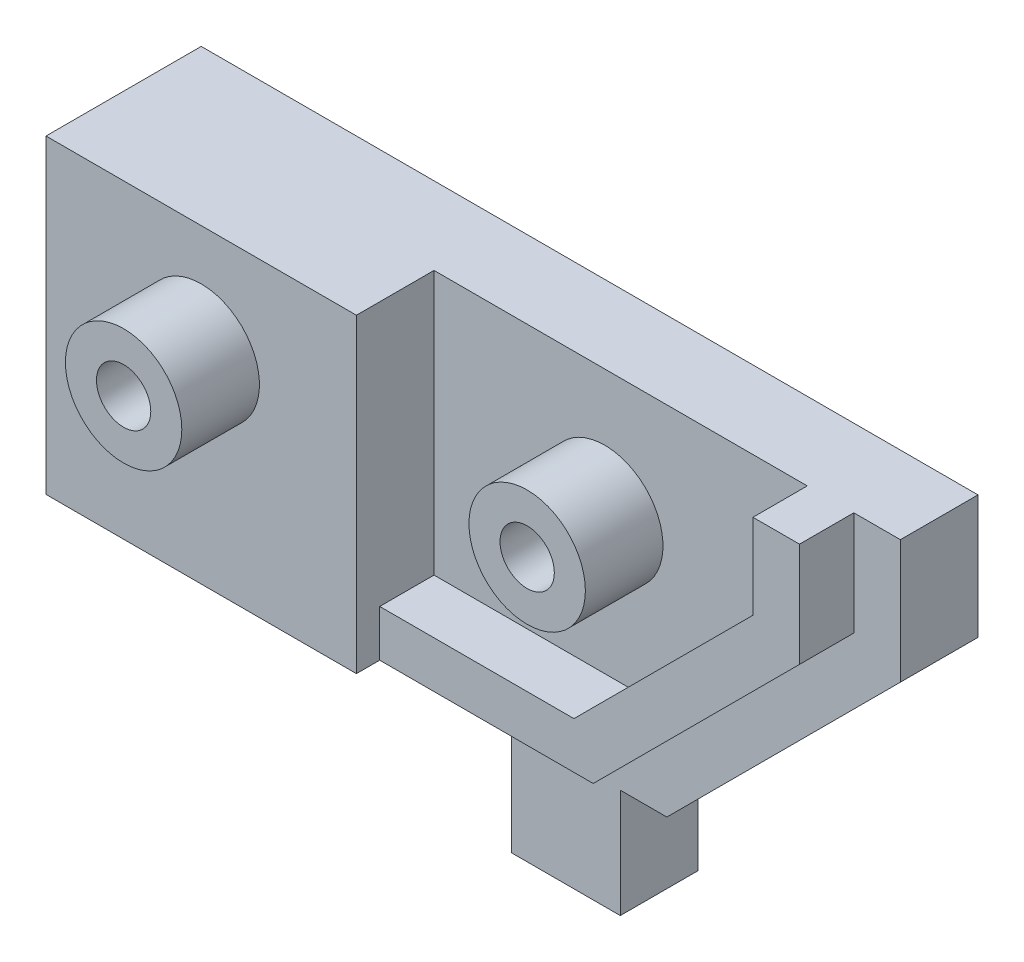
SolidWorks part; units mm, degrees
ref_plane "Front Plane" through (0, 0, 0) normal (0, 0, 1) x (1, 0, 0)
ref_plane "Top Plane" through (0, 0, 0) normal (0, 1, 0) x (1, 0, 0)
ref_plane "Right Plane" through (0, 0, 0) normal (1, 0, 0) x (0, 0, -1)
sketch "Sketch1" plane through (0, 0, 0) normal (0, 1, 0) x (1, 0, 0)
  line L10 (-18, -5.5617) -> (-18, -10) construction
  line L11 (0, 0) -> (-18, 0)
  line L12 (0, 0) -> (0, -5)
  line L13 (0, -5) -> (-15, -5)
  line L14 (-18, 0) -> (-18, -5.5617) construction
  line L16 (-15, -5) -> (-15, -10)
  line L17 (-15, -10) -> (-35, -10)
  line L18 (-35, -5) -> (-35, -10)
  line L19 (-18, 0) -> (-22, 0)
  line L21 (-35, -5) -> (-35, 0)
  line L22 (-35, 0) -> (-22, 0)
  dimension "D1" = 20
  dimension "D2" = 5
  dimension "D3" = 5
  dimension "D4" = 18
  dimension "D7" = 15
extrude "Boss-Extrude1" add sketch "Sketch1" along normal blind 23
sketch "Sketch2" plane through (0, 0, 10) normal (0, 0, 1) x (1, 0, 0)
  line L0 (-35, 23) -> (-35, 0) construction
  line L1 (-35, 0) -> (-15, 0) construction
  line L2 (-15, 0) -> (0, 0) construction
  line L3 (0, 23) -> (0, 0) construction
  circle A0 centre (-25, 16) radius 1.75
  circle A1 centre (-4, 15) radius 1.75
  dimension "D5" = 3.5
  dimension "D6" = 3.5
  dimension "D1" = 10
  dimension "D2" = 16
  dimension "D3" = 15
  dimension "D4" = 4
extrude "Cut-Extrude1" cut sketch "Sketch2" against normal through all
sketch "Sketch3" plane through (0, 0, 0) normal (0, -1, 0) x (1, 0, 0)
  line L0 (-25, 10) -> (-25, 0) construction
  line L1 (-35, 10) -> (-15, 10) construction
  line L3 (0, 0) -> (-35, 0) construction
  line L5 (0, 2.5) -> (-35, 2.5) construction
  line L6 (0, 5) -> (0, 0) construction
  line L7 (-35, 0) -> (-35, 10) construction
  circle A1 centre (-25, 2.5) radius 1.5
  dimension "D1" = 3
extrude "Cut-Extrude2" cut sketch "Sketch3" against normal blind 10
sketch "Sketch4" plane through (0, 0, 0) normal (0, -1, 0) x (1, 0, 0)
  line L0 (-35, 2.5) -> (0, 2.5) construction
  line L2 (0, 5) -> (0, 0) construction
  line L3 (-35, 0) -> (-35, 10) construction
  line L6 (-15, 5) -> (0, 5) construction
  line L7 (-10, 0) -> (-3, 0)
  line L8 (-10, 0) -> (-10, 5)
  line L9 (-10, 5) -> (-3, 5)
  line L10 (-3, 0) -> (-3, 5)
  line L11 (-10, 0) -> (-3, 5) construction
  line L12 (-10, 5) -> (-3, 0) construction
  point P12 (-6.5, 2.5)
  dimension "D1" = 7
  dimension "D3" = 3
extrude "Boss-Extrude2" add sketch "Sketch4" along normal blind 7
sketch "Sketch5" plane through (0, 0, 10) normal (0, 0, 1) x (1, 0, 0)
  circle A0 centre (-25, 16) radius 1.75
  circle A1 centre (-25, 16) radius 3.75
  circle A2 centre (-25, 16) radius 1.75 construction
  dimension "D1" = 2
extrude "Boss-Extrude3" add sketch "Sketch5" along normal blind 5
sketch "Sketch6" plane through (0, 0, 5) normal (0, 0, 1) x (1, 0, 0)
  circle A0 centre (-4, 15) radius 1.75
  circle A1 centre (-4, 15) radius 1.75 construction
  circle A2 centre (-4, 15) radius 3.75
  dimension "D1" = 2
extrude "Boss-Extrude4" add sketch "Sketch6" along normal blind 5
sketch "Sketch7" plane through (0, 0, 5) normal (0, 0, 1) x (1, 0, 0)
  line L0 (0, 0) -> (0, 23)
  line L1 (0, 23) -> (15.0472, 23)
  line L2 (15.0472, 15.0472) -> (0, 0)
  line L3 (15.0472, 23) -> (15.0472, 15.0472)
  dimension "D1" = 45
  dimension "D2" = 21.28
extrude "Boss-Extrude5" add sketch "Sketch7" against normal blind 5
sketch "Sketch8" plane through (0, 0, 5) normal (0, 0, 1) x (1, 0, 0)
  line L0 (12.0472, 23) -> (12.0472, 16.2899)
  line L1 (-15, 23) -> (15.0472, 23) construction
  line L2 (12.0472, 16.2899) -> (-1.2426, 3)
  line L3 (-1.2426, 3) -> (-15, 3)
  line L4 (-15, 23) -> (-15, 0) construction
  line L5 (15.0472, 15.0472) -> (15.0472, 23) construction
  line L6 (0, 0) -> (15.0472, 15.0472) construction
  line L7 (-15, 0) -> (-10, 0) construction
  line L8 (9.0472, 23) -> (9.0472, 17.5325)
  line L9 (9.0472, 17.5325) -> (-2.4853, 6)
  line L10 (-2.4853, 6) -> (-15, 6)
  line L11 (9.0472, 23) -> (12.0472, 23)
  line L12 (-15, 6) -> (-15, 3)
  dimension "D1" = 3
  dimension "D2" = 3
  dimension "D3" = 3
  dimension "D4" = 3
extrude "Boss-Extrude6" add sketch "Sketch8" along normal blind 3.5
sketch "Sketch9" plane through (-15, 0, 0) normal (1, 0, 0) x (0, 0, -1)
  line L1 (-5, 3) -> (-10, 3)
  line L2 (-5, 3) -> (-5, 0)
  line L3 (-5, 0) -> (-10, 0)
  line L4 (-10, 3) -> (-10, 0)
extrude "Cut-Extrude3" cut sketch "Sketch9" against normal up to surface (20 mm away) contours L2 L1 L4 L3 up to face at (-35, 11.5, 5)
sketch "Sketch10" plane through (0, 0, 0) normal (0, 0, -1) x (-1, 0, 0)
  circle A0 centre (4, 15) radius 2.5
  circle A1 centre (25, 16) radius 2.5
  dimension "D1" = 5
  dimension "D2" = 5
extrude "Cut-Extrude4" cut sketch "Sketch10" against normal blind 4
